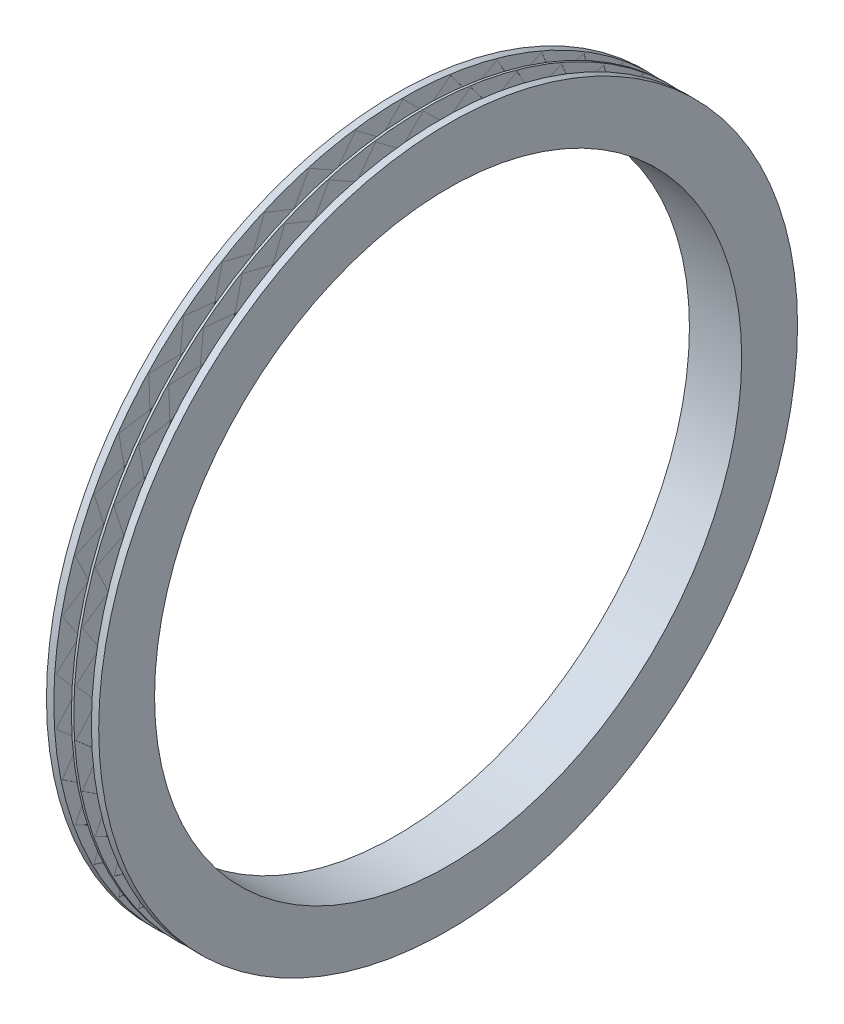
SolidWorks part; units mm, degrees
ref_plane "Ön Düzlem" through (0, 0, 0) normal (0, 0, 1) x (1, 0, 0)
ref_plane "Üst Düzlem" through (0, 0, 0) normal (0, 1, 0) x (1, 0, 0)
ref_plane "Sağ Düzlem" through (0, 0, 0) normal (1, 0, 0) x (0, 0, -1)
sketch "Sketch1" plane through (0, 0, 0) normal (0, 0, 1) x (1, 0, 0)
  line L0 (-178.25, 2385) -> (-178.25, 2003.6)
  line L1 (-178.25, 2003.6) -> (178.25, 2003.6)
  line L2 (178.25, 2003.6) -> (178.25, 2385)
  line L3 (178.25, 2385) -> (128.25, 2385)
  line L4 (128.25, 2385) -> (128.25, 2027.4)
  line L5 (128.25, 2027.4) -> (7.95, 2027.4)
  line L6 (7.95, 2027.4) -> (7.95, 2385)
  line L7 (7.95, 2385) -> (-7.95, 2385)
  line L8 (-7.95, 2385) -> (-7.95, 2027.4)
  line L9 (-7.95, 2027.4) -> (-128.25, 2027.4)
  line L10 (-128.25, 2027.4) -> (-128.25, 2385)
  line L11 (-128.25, 2385) -> (-178.25, 2385)
  line L12 (-3265.7256, 0) -> (1904.0878, 0) construction
  point P9 (0, 2385)
  dimension "D1" = 2003.6
  dimension "D2" = 2027.4
  dimension "D3" = 2385
  dimension "D4" = 120.3
  dimension "D5" = 15.9
  dimension "D6" = 50
revolve "Revolve1" add sketch "Sketch1" angle 360 about L12
sketch "Sketch3" plane through (-128.25, 0, 0) normal (1, 0, 0) x (0, 0, -1)
  line L0 (0, 0) -> (0, 3969.0988) construction
  line L1 (-152.6644, 2223.162) -> (0, 2375.8263)
  line L2 (-152.6644, 2223.162) -> (0, 2070.4976)
  line L3 (0, 2375.8263) -> (152.6644, 2223.162)
  line L4 (0, 2070.4976) -> (152.6644, 2223.162)
  line L5 (196.075, 0) -> (-196.075, 0) construction
  point P3 (0, 0)
  point P6 (0, 0)
  point P9 (0, 2375.8263)
  point P11 (0, 0)
  point P12 (0, 0)
  dimension "D1" = 215.9
extrude "Cut-Extrude16" cut sketch "Sketch3" against normal blind 1
ref_plane "Plane3" through (-68.1, 0, 0) normal (1, 0, 0) x (0, 0, -1)
mirror "Mirror5" about plane through (-68.1, 0, 0) normal (1, 0, 0) of "Cut-Extrude16"
mirror "Mirror6" about plane through (0, 0, 0) normal (1, 0, 0) of "Cut-Extrude16", "Mirror5"
pattern_circular "CirPattern1" count 46 over 360 about axis through (0, 0, 0) along (1, 0, 0) of "Mirror6", "Cut-Extrude16", "Mirror5"
